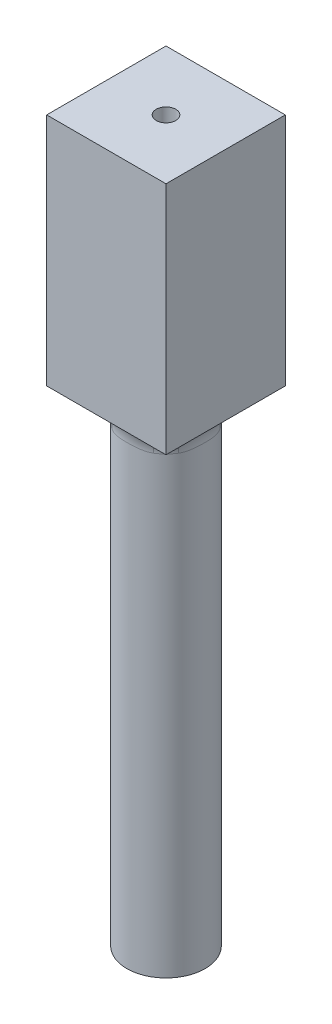
SolidWorks part; units mm, degrees
ref_plane "Front Plane" through (0, 0, 0) normal (0, 0, 1) x (1, 0, 0)
ref_plane "Top Plane" through (0, 0, 0) normal (0, 1, 0) x (1, 0, 0)
ref_plane "Right Plane" through (0, 0, 0) normal (1, 0, 0) x (0, 0, -1)
sketch "Sketch1" plane through (0, 0, 0) normal (0, 1, 0) x (1, 0, 0)
  circle A0 centre (0, 0) radius 5
  dimension "D1" = 10
extrude "Boss-Extrude1" add sketch "Sketch1" along normal blind 62
sketch "Sketch3" plane through (0, 62, 0) normal (0, 1, 0) x (1, 0, 0)
  line L1 (-7.625, -7.625) -> (7.625, -7.625)
  line L2 (-7.625, -7.625) -> (-7.625, 7.625)
  line L3 (-7.625, 7.625) -> (7.625, 7.625)
  line L4 (7.625, -7.625) -> (7.625, 7.625)
  line L5 (-7.625, -7.625) -> (7.625, 7.625) construction
  line L6 (-7.625, 7.625) -> (7.625, -7.625) construction
  point P0 (0, 0)
  dimension "D1" = 15.25
  dimension "D2" = 15.25
extrude "Boss-Extrude2" add sketch "Sketch3" along normal blind 30
sketch "Sketch4" plane through (0, 92, 0) normal (0, 1, 0) x (1, 0, 0)
  circle A0 centre (0, 0) radius 1.25
  dimension "D1" = 2.5
sketch "Sketch5" plane through (0, 0, 0) normal (0, -1, 0) x (1, 0, 0)
  circle A0 centre (0, 0) radius 3
  dimension "D1" = 6
extrude "Cut-Extrude1" cut sketch "Sketch5" against normal blind 10
fillet "Fillet1" radius 4 1 edges at (0, 62, 5)
extrude "Cut-Extrude2" cut sketch "Sketch4" against normal blind 15
